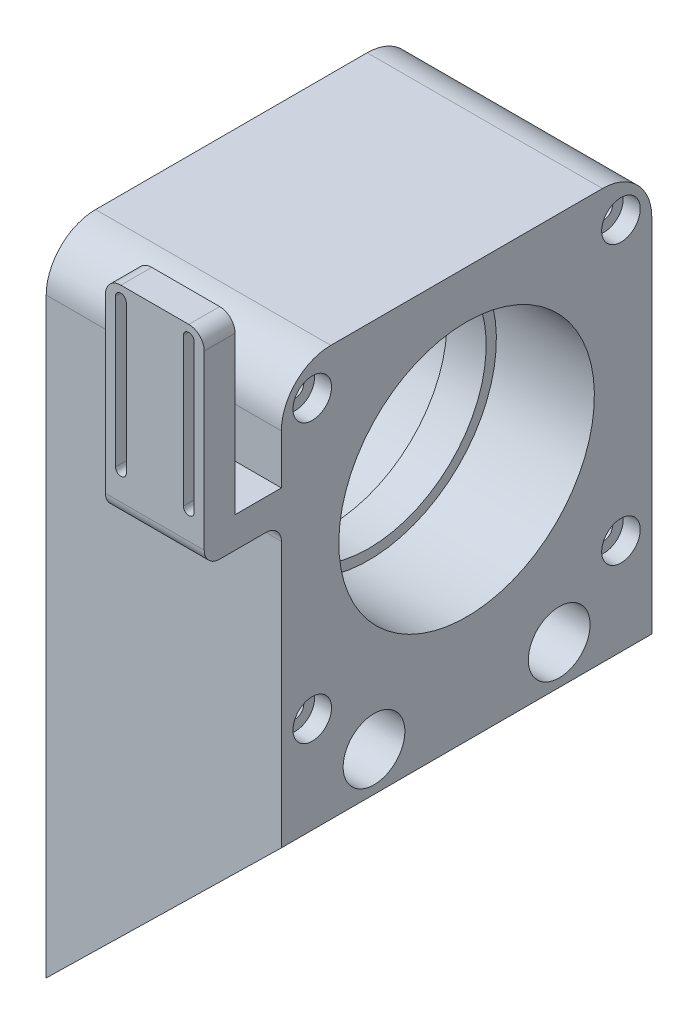
SolidWorks part; units mm, degrees
ref_plane "Front Plane" through (0, 0, 0) normal (0, 0, 1) x (1, 0, 0)
ref_plane "Top Plane" through (0, 0, 0) normal (0, 1, 0) x (1, 0, 0)
ref_plane "Right Plane" through (0, 0, 0) normal (1, 0, 0) x (0, 0, -1)
sketch "Sketch1" plane through (0, 0, 0) normal (0, 0, 1) x (1, 0, 0)
  line L0 (381, 457.2) -> (457.2, 457.2)
  line L1 (457.2, 457.2) -> (457.2, 431.8)
  line L2 (381, 457.2) -> (381, 357.2)
  line L5 (381, 357.2) -> (457.2, 431.8)
  dimension "D1" = 76.2
  dimension "D2" = 100
extrude "Boss-Extrude1" add sketch "Sketch1" along normal blind 120
sketch "Sketch3" plane through (457.2, 0, 0) normal (1, 0, 0) x (0, 0, -1)
  line L1 (-120, 431.8) -> (0, 431.8)
  line L2 (-120, 431.8) -> (-120, 357.2)
  line L3 (-120, 357.2) -> (0, 357.2)
  line L4 (0, 431.8) -> (0, 357.2)
  circle A0 centre (-90, 394.5) radius 4.25
  circle A1 centre (-30, 394.5) radius 4.25
  circle A2 centre (-90, 444.5) radius 4.25
  circle A3 centre (-30, 444.5) radius 4.25
  dimension "D1" = 30
  dimension "D2" = 30
  dimension "D3" = 37.3
  dimension "D4" = 37.3
extrude "Cut-Extrude1" cut sketch "Sketch3" against normal blind 120 contours A1 | A0
sketch "Sketch5" plane through (457.2, 0, 0) normal (1, 0, 0) x (0, 0, -1)
  circle A0 centre (-90, 394.5) radius 10
  circle A1 centre (-30, 394.5) radius 10
  circle A2 centre (-90, 444.5) radius 10
  circle A3 centre (-30, 444.5) radius 10
extrude "Cut-Extrude2" cut sketch "Sketch5" against normal blind 53
sketch "Sketch6" plane through (457.2, 0, 0) normal (1, 0, 0) x (0, 0, -1)
  circle A0 centre (-90, 444.5) radius 4.25
  circle A1 centre (-30, 444.5) radius 4.25
extrude "Cut-Extrude3" cut sketch "Sketch6" against normal blind 103
sketch "Sketch7" plane through (0, 457.2, 0) normal (0, 1, 0) x (1, 0, 0)
  line L1 (381, 0) -> (457.2, 0)
  line L2 (381, 0) -> (381, -120)
  line L3 (381, -120) -> (457.2, -120)
  line L4 (457.2, 0) -> (457.2, -120)
extrude "Boss-Extrude2" add sketch "Sketch7" along normal blind 101.6
sketch "Sketch8" plane through (381, 0, 0) normal (-1, 0, 0) x (0, 0, 1)
  line L0 (120, 457.2) -> (0, 457.2)
  line L1 (120, 558.8) -> (120, 357.2) construction
  line L2 (0, 558.8) -> (0, 357.2) construction
  line L3 (0, 558.8) -> (120, 558.8) construction
  circle A0 centre (60, 508) radius 41.4
  dimension "D1" = 101.6
  dimension "D2" = 50.8
extrude "Cut-Extrude4" cut sketch "Sketch8" against normal blind 31.75 contours A0 region at (381, 508, 60)
sketch "Sketch9" plane through (457.2, 0, 0) normal (1, 0, 0) x (0, 0, -1)
  line L0 (-120, 558.8) -> (0, 558.8) construction
  line L1 (-120, 431.8) -> (-120, 558.8) construction
  circle A0 centre (-60, 508) radius 41.4
  dimension "D1" = 50.8
  dimension "D2" = 60
extrude "Cut-Extrude5" cut sketch "Sketch9" against normal blind 31.75
sketch "Sketch10" plane through (457.2, 0, 0) normal (1, 0, 0) x (0, 0, -1)
  circle A0 centre (-60, 508) radius 38.1
extrude "Cut-Extrude6" cut sketch "Sketch10" against normal blind 76.2
sketch "Sketch13" plane through (0, 558.8, 0) normal (0, 1, 0) x (1, 0, 0)
  line L1 (381, 0) -> (457.2, 0)
  line L2 (381, 0) -> (381, -120)
  line L3 (381, -120) -> (457.2, -120)
  line L4 (457.2, 0) -> (457.2, -120)
extrude "Boss-Extrude3" add sketch "Sketch13" along normal blind 6
sketch "Sketch11" plane through (457.2, 0, 0) normal (1, 0, 0) x (0, 0, -1)
  line L0 (-120, 431.8) -> (-120, 564.8) construction
  line L1 (-110, 553) -> (-10, 553)
  line L2 (-110, 553) -> (-110, 463)
  line L3 (-110, 463) -> (-10, 463)
  line L4 (-10, 553) -> (-10, 463)
  line L5 (0, 431.8) -> (0, 564.8) construction
  circle A0 centre (-60, 508) radius 5.3331
  circle A1 centre (-110, 553) radius 2.75
  circle A2 centre (-10, 553) radius 2.75
  circle A3 centre (-10, 463) radius 2.75
  circle A4 centre (-110, 463) radius 2.75
  dimension "D1" = 10
  dimension "D2" = 10
  dimension "D3" = 45
  dimension "D4" = 90
extrude "Cut-Extrude7" cut sketch "Sketch11" against normal blind 84.4 contours L1 A1 L2 | L2 A1 L1 | L4 A2 L1 | L1 A2 L4 | L3 A3 L4 | L4 A3 L3 | L2 A4 L3 | L3 A4 L2 region at (457.2, 553.389, 110.389) region at (457.2, 551.8329, 108.8329) region at (457.2, 553.389, 9.611) region at (457.2, 551.8329, 11.1671) region at (457.2, 464.1671, 108.8329) region at (457.2, 462.611, 110.389) region at (457.2, 462.611, 9.611) region at (457.2, 464.1671, 11.1671)
sketch "Sketch12" plane through (457.2, 0, 0) normal (1, 0, 0) x (0, 0, -1)
  circle A0 centre (-110, 553) radius 6.25
  circle A1 centre (-10, 553) radius 6.25
  circle A2 centre (-10, 463) radius 6.25
  circle A3 centre (-110, 463) radius 6.25
extrude "Cut-Extrude8" cut sketch "Sketch12" against normal blind 5.5
fillet "Fillet1" radius 16 2 edges at (419.1, 564.8, 0) (419.1, 564.8, 120)
sketch "Sketch18" plane through (0, 0, 120) normal (0, 0, 1) x (1, 0, 0)
  line L0 (457.2, 431.8) -> (457.2, 548.8) construction
  line L1 (457.2, 522.8) -> (425.2, 522.8)
  line L2 (457.2, 522.8) -> (457.2, 532.8)
  line L3 (457.2, 532.8) -> (425.2, 532.8)
  line L4 (425.2, 522.8) -> (425.2, 532.8)
  line L6 (381, 564.8) -> (457.2, 564.8) construction
  dimension "D1" = 32
  dimension "D2" = 32
  dimension "D3" = 10
extrude "Boss-Extrude6" add sketch "Sketch18" along normal blind 15
sketch "Sketch20" plane through (0, 0, 135) normal (0, 0, 1) x (1, 0, 0)
  line L0 (431.95, 584.6825) -> (431.95, 536.8)
  line L2 (425.2, 532.8) -> (425.2, 588.6825)
  line L3 (425.2, 588.6825) -> (457.2, 588.6825)
  line L4 (457.2, 536.6825) -> (457.2, 588.6825)
  line L5 (428.45, 584.6825) -> (428.45, 536.8)
  line L6 (450.45, 584.6825) -> (450.45, 536.8)
  line L7 (450.45, 584.6825) -> (450.45, 536.8)
  line L8 (425.2, 532.8) -> (425.2, 522.8)
  line L9 (425.2, 522.8) -> (457.2, 522.8)
  line L10 (457.2, 522.8) -> (457.2, 536.6825)
  line L11 (453.95, 584.6825) -> (453.95, 536.8)
  circle A0 centre (430.2, 584.6825) radius 1.75
  circle A1 centre (452.2, 584.6825) radius 1.75
  circle A2 centre (452.2, 536.8) radius 1.75
  circle A3 centre (430.2, 536.8) radius 1.75
  line M6 (457.2, 522.8) -> (457.2, 532.8)
  line M7 (457.2, 532.8) -> (425.2, 532.8)
  line M8 (425.2, 532.8) -> (425.2, 522.8)
  line M9 (425.2, 522.8) -> (457.2, 522.8)
  dimension "D1" = 22
  dimension "D2" = 22
  dimension "D3" = 5
  dimension "D4" = 52
  dimension "D5" = 4
  dimension "D6" = 5
  dimension "D7" = 4
extrude "Boss-Extrude7" add sketch "Sketch20" along normal blind 10 contours L4 L3 L2 A3 L5 A0 L0 A2 L6 A1 L7 M7 | M9 M6 M7 M8 region at (441.2, 527.8, 135) region at (441.2, 560.7413, 135)
fillet "Fillet3" radius 5 4 edges at (441.2, 522.8, 145) (425.2, 588.6825, 140) (457.2, 588.6825, 140) (441.2, 522.8, 120)
